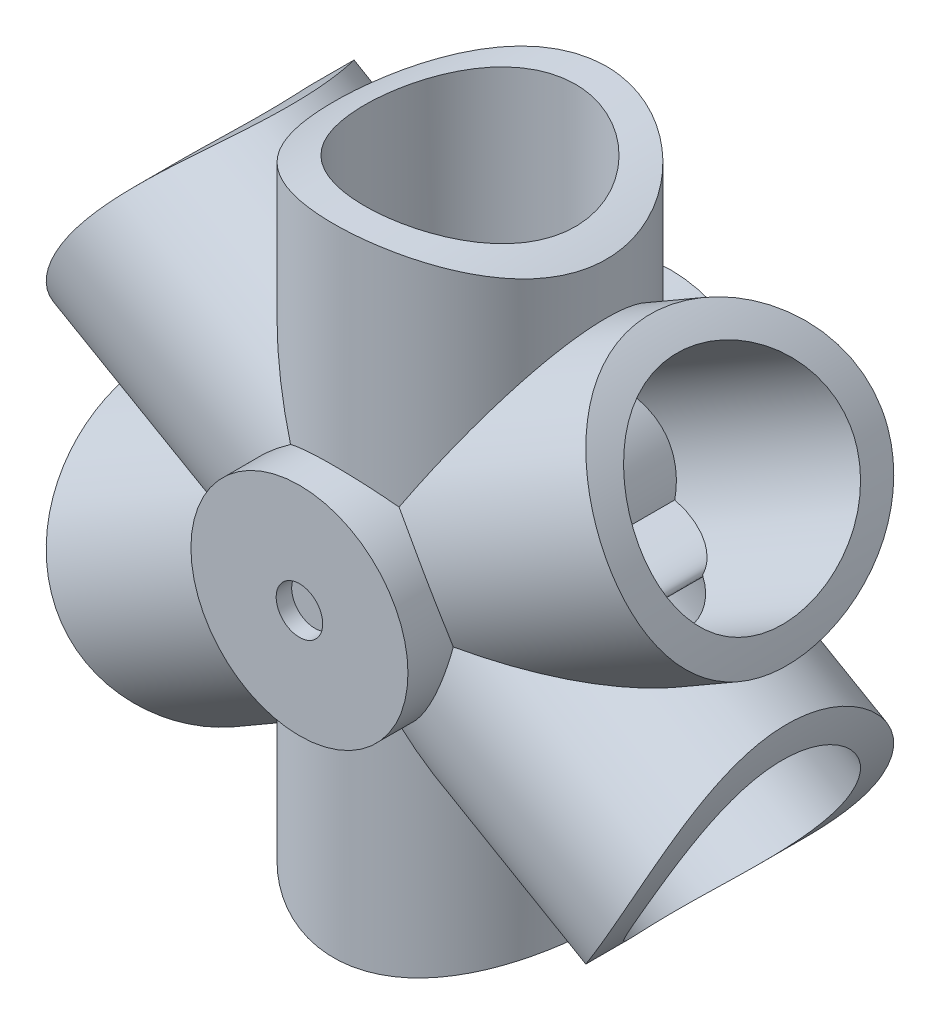
SolidWorks part; units mm, degrees
ref_plane "Front Plane" through (0, 0, 0) normal (0, 0, 1) x (1, 0, 0)
ref_plane "Top Plane" through (0, 0, 0) normal (0, 1, 0) x (1, 0, 0)
ref_plane "Right Plane" through (0, 0, 0) normal (1, 0, 0) x (0, 0, -1)
sketch "Sketch1" plane through (0, 0, 0) normal (0, 1, 0) x (1, 0, 0)
  circle A0 centre (0, 0) radius 11.176
  circle A1 centre (0, 0) radius 8.636
  dimension "D1" = 22.352
  dimension "D2" = 17.272
extrude "Boss-Extrude1" add sketch "Sketch1" along normal blind 20.32
sketch "Sketch2" plane through (0, 0, 0) normal (0, 0, 1) x (1, 0, 0)
  line L0 (11.176, 20.32) -> (-11.176, 20.32) construction
  line L1 (-8.636, 20.32) -> (-11.176, 20.32)
  line L2 (8.4632, 20.32) -> (11.0032, 20.32)
  line L3 (0, 20.32) -> (0, 38.4954) construction
  arc A2 (8.4632, 20.32) -> (-8.636, 20.32) centre (-0.0864, 7.6039) ccw
  arc A3 (11.0032, 20.32) -> (-11.176, 20.32) centre (-0.0864, 7.6039) ccw
revolve "Revolve1" add sketch "Sketch2" angle 360 about L3 region at (-9.906, 20.5457, 0)
ref_plane "Plane1" through (0, 27.94, 0) normal (0, -1, 0) x (-1, 0, 0)
sketch "Sketch3" plane through (0, 27.94, 0) normal (0, -1, 0) x (-1, 0, 0)
  line L0 (0, 11.9871) -> (0, -12.3331)
pattern_circular "CirPattern1" count 6 over 360 about axis through (0, 27.94, -11.9871) along (0, 0, 1) of bodies 103
sketch "Sketch4" plane through (0, 0, 0) normal (0, 0, 1) x (1, 0, 0)
  circle A0 centre (0, 27.94) radius 8.89
extrude "Boss-Extrude2" add sketch "Sketch4" along normal blind 13.97 and the other way blind 16.51
sketch "Sketch5" plane through (0, 0, 13.97) normal (0, 0, 1) x (1, 0, 0)
  circle A0 centre (0, 27.94) radius 26.035
  circle A1 centre (0, 27.94) radius 34.3456
  dimension "D1" = 52.07
extrude "Cut-Extrude1" cut sketch "Sketch5" against normal through all
sketch "Sketch8" plane through (0, 0, 0) normal (0, 1, 0) x (1, 0, 0)
  circle A0 centre (0, 0) radius 8.636
extrude "Cut-Extrude2" cut sketch "Sketch8" along normal up to surface (19.05 mm away) up to face at (0.3119, 19.0769, 4.3067)
pattern_circular "CirPattern2" count 6 over 360 about axis through (0, 27.94, -16.51) along (0, 0, 1) of "Cut-Extrude2"
sketch "Sketch9" plane through (0, 0, -16.51) normal (0, 0, -1) x (-1, 0, 0)
  line L0 (-159.3608, -65.013) -> (-26.0275, -65.013) construction
  line L1 (-5.3001, 25.0893) -> (-5.3001, 24.6378)
  line L2 (-5.3001, 32.5511) -> (5.1143, 32.5511)
  line L3 (-6.5701, 31.2811) -> (-6.5701, 23.7722)
  line L4 (-5.3001, 22.5022) -> (5.1143, 22.5022)
  line L5 (6.3843, 31.2811) -> (6.3843, 23.7722)
  line L6 (-4.9342, 31.6555) -> (4.7922, 31.6555)
  line L7 (-5.6962, 30.8935) -> (-5.6962, 24.1162)
  line L8 (-4.9342, 23.3542) -> (4.7922, 23.3542)
  line L9 (5.5542, 30.8935) -> (5.5542, 24.1162)
  line L10 (-5.3001, 24.6378) -> (-3.6843, 24.6378)
  line L11 (-3.6843, 24.6378) -> (-3.6843, 25.0893)
  line L12 (-3.6843, 25.0893) -> (-4.0153, 25.0893)
  line L13 (-4.0153, 25.0893) -> (-2.7662, 29.1074)
  line L14 (-2.7662, 29.1074) -> (-0.7496, 27.3015)
  line L15 (-0.7496, 27.3015) -> (-0.7496, 24.8635)
  line L16 (-0.7496, 24.8635) -> (-1.5021, 24.8635)
  line L17 (-1.5021, 24.8635) -> (-1.5021, 24.4572)
  line L18 (-1.5021, 24.4572) -> (-0.2379, 24.4572)
  line L19 (-0.2379, 24.4572) -> (-0.2379, 31.2811)
  line L20 (-0.2379, 31.2811) -> (-1.7579, 31.2811)
  line L21 (-1.7579, 31.2811) -> (-1.7579, 30.7478)
  line L22 (-1.7579, 30.7478) -> (-0.7496, 30.7478)
  line L23 (-0.7496, 30.7478) -> (-0.7496, 28.656)
  line L24 (-0.7496, 28.656) -> (-2.6007, 30.507)
  line L25 (-2.6007, 30.507) -> (-4.3163, 25.0893)
  line L26 (-4.3163, 25.0893) -> (-5.3001, 25.0893)
  line L27 (-0.071, 31.6555) -> (-0.071, 23.3542) construction
  line L28 (2.4587, 30.507) -> (4.1743, 25.0893)
  line L29 (0.6076, 28.656) -> (2.4587, 30.507)
  line L30 (0.6076, 30.7478) -> (0.6076, 28.656)
  line L31 (1.6159, 30.7478) -> (0.6076, 30.7478)
  line L32 (1.6159, 31.2811) -> (1.6159, 30.7478)
  line L33 (0.0959, 31.2811) -> (1.6159, 31.2811)
  line L34 (0.0959, 24.4572) -> (0.0959, 31.2811)
  line L35 (1.3601, 24.4572) -> (0.0959, 24.4572)
  line L36 (1.3601, 24.8635) -> (1.3601, 24.4572)
  line L37 (0.6076, 24.8635) -> (1.3601, 24.8635)
  line L38 (0.6076, 27.3015) -> (0.6076, 24.8635)
  line L39 (2.6242, 29.1074) -> (0.6076, 27.3015)
  line L40 (3.8733, 25.0893) -> (2.6242, 29.1074)
  line L41 (3.5422, 25.0893) -> (3.8733, 25.0893)
  line L42 (3.5422, 24.6378) -> (3.5422, 25.0893)
  line L43 (5.158, 24.6378) -> (3.5422, 24.6378)
  line L44 (5.158, 25.0893) -> (5.158, 24.6378)
  line L45 (4.1743, 25.0893) -> (5.158, 25.0893)
  line L47 (-5.3001, 24.3067) -> (5.1143, 24.3067)
  line L48 (-5.3001, 24.3067) -> (-5.3001, 23.8703)
  line L49 (-5.3001, 23.8703) -> (5.1143, 23.8703)
  line L50 (5.1143, 24.3067) -> (5.1143, 23.8703)
  arc A0 (5.1143, 32.5511) -> (6.3843, 31.2811) centre (5.1143, 31.2811) cw
  arc A1 (5.1143, 22.5022) -> (6.3843, 23.7722) centre (5.1143, 23.7722) ccw
  arc A2 (-6.5701, 23.7722) -> (-5.3001, 22.5022) centre (-5.3001, 23.7722) ccw
  arc A3 (-5.3001, 32.5511) -> (-6.5701, 31.2811) centre (-5.3001, 31.2811) ccw
  arc A4 (4.7922, 31.6555) -> (5.5542, 30.8935) centre (4.7922, 30.8935) cw
  arc A5 (4.7922, 23.3542) -> (5.5542, 24.1162) centre (4.7922, 24.1162) ccw
  arc A6 (-5.6962, 24.1162) -> (-4.9342, 23.3542) centre (-4.9342, 24.1162) ccw
  arc A7 (-4.9342, 31.6555) -> (-5.6962, 30.8935) centre (-4.9342, 30.8935) ccw
  dimension "D1" = 1.27
  dimension "D2" = 0.762
extrude "Cut-Extrude3" cut sketch "Sketch9" against normal blind 1.27 contours L25 L26 L1 L10 L11 L12 L13 L14 L15 L16 L17 L18 L19 L20 L21 L22 L23 L24 | L45 L28 L29 L30 L31 L32 L33 L34 L35 L36 L37 L38 L39 L40 L41 L42 L43 L44 | L2 A3 L3 A2 L4 A1 L5 A0 A7 L6 A4 L9 A5 L8 A6 L7 region at (4.8082, 25.0043, -16.51) region at (0.0929, 32.3872, -16.51) region at (-3.2355, 27.7725, -16.51)
sketch "Sketch10" plane through (0, 0, 13.97) normal (0, 0, 1) x (1, 0, 0)
  circle A0 centre (0, 27.94) radius 1.905
  arc A1 (-4.445, 35.639) -> (-8.89, 27.94) centre (0, 27.94) ccw construction
  dimension "D1" = 3.81
extrude "Cut-Extrude4" cut sketch "Sketch10" against normal blind 1.27 contours A0
sketch "Sketch12" plane through (0, 0, 0) normal (0, 0, 1) x (1, 0, 0)
  line L1 (-8.89, 27.94) -> (-17.272, 27.94) construction
  arc A2 (-4.445, 35.639) -> (-8.89, 27.94) centre (0, 27.94) ccw construction
  ellipse E0 centre (-8.89, 27.94) end of major axis (-13.97, 27.94) minor radius 1.27
  dimension "D1" = 10.16
  dimension "D2" = 2.54
extrude "Boss-Extrude3" add sketch "Sketch12" along normal up to next and the other way up to next
pattern_circular "CirPattern3" count 6 over 360 about axis through (0, 27.94, -16.51) along (0, 0, 1) of "Boss-Extrude3"
